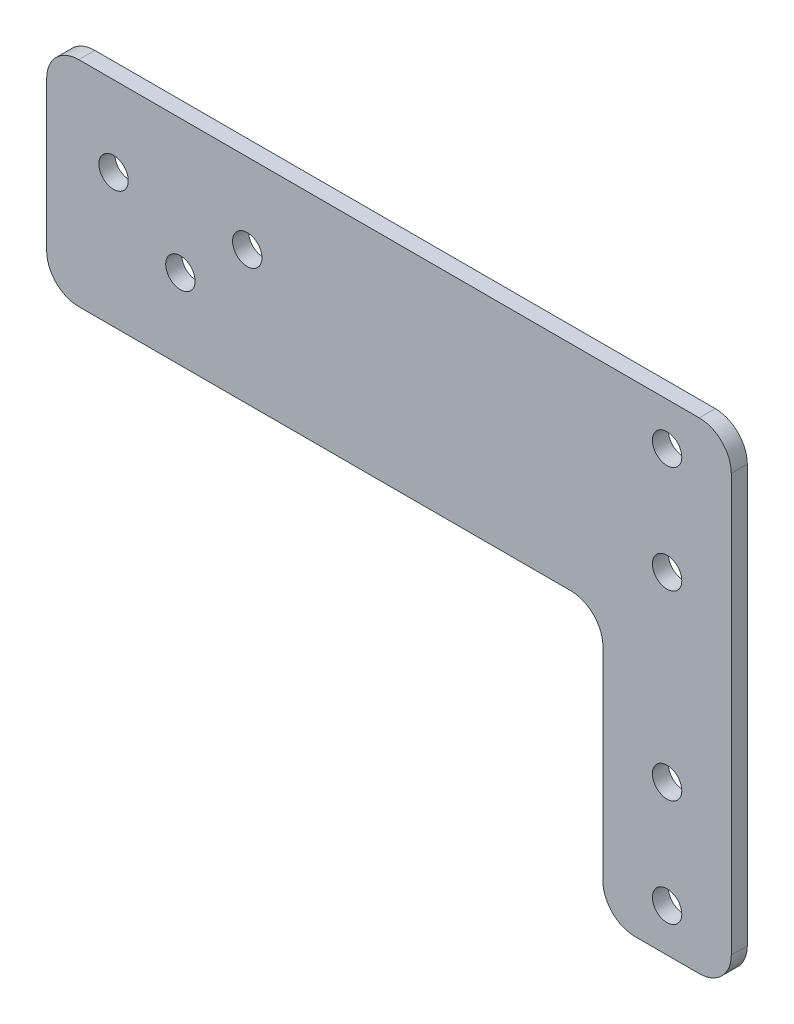
SolidWorks part; units mm, degrees
material "6063-T1"
ref_plane "Płaszczyzna przednia" through (0, 0, 0) normal (0, 0, 1) x (1, 0, 0)
ref_plane "Płaszczyzna górna" through (0, 0, 0) normal (0, 1, 0) x (1, 0, 0)
ref_plane "Płaszczyzna prawa" through (0, 0, 0) normal (1, 0, 0) x (0, 0, -1)
sketch "Szkic1" plane through (0, 0, 0) normal (0, 0, 1) x (1, 0, 0)
  line L0 (0, 0) -> (-104, 0)
  line L1 (-104, 0) -> (-104, 40)
  line L2 (-104, 40) -> (24, 40)
  line L3 (24, 40) -> (24, -50)
  line L4 (24, -50) -> (0, -50)
  line L5 (0, -50) -> (0, 0)
  dimension "D1" = 90
  dimension "D2" = 24
  dimension "D3" = 128
  dimension "D4" = 40
base flange "Odgięcie bazowe1" sketch "Szkic1" thickness 3 reverse thickness direction no parameters "D1"=3
hole_wizard "Otwór pod śrubę M51" positions "Szkic6" profile "Szkic7" hole size "M5" standard "ISO" end condition through all
sketch "Szkic6" plane through (0, 0, 0) normal (0, 0, 1) x (1, 0, 0)
  line L0 (0, -50) -> (24, -50) construction
  line L1 (12, -50) -> (12, 40) construction
  line L2 (24, 40) -> (-104, 40) construction
  line L4 (-91.5, 25) -> (-66.5, 25) construction
  line L6 (-79, 25) -> (-79, 15) construction
  line L8 (-104, 40) -> (-104, 0) construction
  point P0 (12, -42)
  point P2 (12, -22)
  point P4 (12, 12)
  point P6 (12, 32)
  point P18 (-91.5, 25)
  point P20 (-66.5, 25)
  point P22 (-79, 15)
  dimension "D1" = 20
  dimension "D2" = 20
  dimension "D3" = 34
  dimension "D4" = 8
  dimension "D5" = 12.5
  dimension "D6" = 15
  dimension "D7" = 25
  dimension "D8" = 10
sketch "Szkic7" plane through (12, -42, 0) normal (1, 0, 0) x (0, -1, 0)
  line L0 (0, 0) -> (0, 3)
  line L1 (0, 3) -> (2.75, 3)
  line L2 (2.75, 3) -> (2.75, 0)
  line L5 (2.75, 0) -> (0, 0)
  line L11 (0, -6.35) -> (0, 107.95) construction
  dimension "Średnica otworu na wylot" = 5.5
  dimension "Głębokość otworu na wylot" = 3
fillet "Zaokrąglenie1" radius 6 6 edges at (24, 40, -1.5) (24, -50, -1.5) (0, -50, -1.5) (0, 0, -1.5) (-104, 0, -1.5) (-104, 40, -1.5)
sketch "Linie zgięcia1" [suppressed] plane through (0, 0, 0) normal (0, 1, 0) x (1, 0, 0)
sketch "Ramka-graniczna1" [suppressed] plane through (0, 0, 0) normal (0, 1, 0) x (1, 0, 0)
sheet metal parameters "Arkusz blachy21" thickness 3 parameters "D1"=3
flat pattern "Rozłożony model21" [suppressed]
sketch "Linie zgięcia2" plane through (0, 0, 0) normal (0, 1, 0) x (1, 0, 0)
sketch3d "Ramka-graniczna2" [suppressed]
  line L0 (-80, -50, 0) -> (24, -50, 0) construction
  line L1 (-80, 40, 0) -> (24, 40, 0) construction
  line L2 (-80, -50, 0) -> (-80, 40, 0) construction
  line L3 (24, -50, 0) -> (24, 40, 0) construction
sheet metal parameters "Arkusz blachy22" thickness 3 parameters "D1"=3
flat pattern "Rozłożony model21"
sketch "Linie zgięcia2" plane through (0, 0, 0) normal (0, 1, 0) x (1, 0, 0)
sketch3d "Ramka-graniczna2" [suppressed]
  line L0 (-104, 40, 0) -> (24, 40, 0) construction
  line L1 (-104, -50, 0) -> (24, -50, 0) construction
  line L2 (-104, 40, 0) -> (-104, -50, 0) construction
  line L3 (24, 40, 0) -> (24, -50, 0) construction
